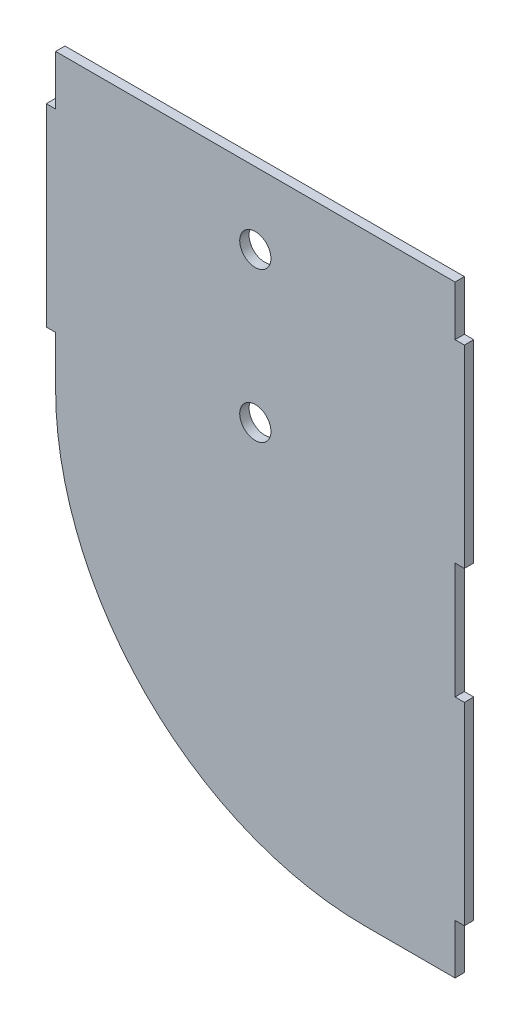
SolidWorks part; units mm, degrees
ref_plane "Front Plane" through (0, 0, 0) normal (0, 0, 1) x (1, 0, 0)
ref_plane "Top Plane" through (0, 0, 0) normal (0, 1, 0) x (1, 0, 0)
ref_plane "Right Plane" through (0, 0, 0) normal (1, 0, 0) x (0, 0, -1)
sketch "Sketch1" plane through (0, 0, 0) normal (0, 0, 1) x (1, 0, 0)
  line L0 (0, 74.6125) -> (-203.2, 74.6125)
  line L1 (0, 87.3125) -> (4.7625, 87.3125) construction
  line L2 (-203.2, 65.0875) -> (-203.2, -65.0875) construction
  line L4 (-203.2, 74.6125) -> (-203.2, 49.2125)
  line L5 (-203.2, 49.2125) -> (-207.9625, 49.2125)
  line L6 (-45.7679, -232.0446) -> (0, -232.0446)
  line L7 (0, -238.3946) -> (0, -206.6446) construction
  line L8 (0, -232.0446) -> (0, -206.6446)
  line L9 (-203.2, -74.6125) -> (-203.2, -49.2125)
  line L10 (-203.2, -49.2125) -> (-207.9625, -49.2125)
  line L11 (0, -206.6446) -> (4.7625, -206.6446) construction
  line L12 (-207.9625, -49.2125) -> (-207.9625, 49.2125)
  line L14 (0, -206.6446) -> (4.7625, -206.6446)
  line L15 (0, 65.0875) -> (0, 80.9625) construction
  line L16 (0, 74.6125) -> (0, 49.2125)
  line L17 (0, -65.0875) -> (0, 65.0875) construction
  line L18 (4.7625, -206.6446) -> (4.7625, -108.2196)
  line L20 (4.7625, -108.2196) -> (0, -108.2196)
  line L22 (0, -108.2196) -> (0, -49.2125) construction
  line L23 (0, -108.2196) -> (0, -49.2125)
  line L24 (0, -49.2125) -> (4.7625, -49.2125)
  line L25 (4.7625, -49.2125) -> (4.7625, 49.2125)
  line L26 (4.7625, 49.2125) -> (0, 49.2125)
  line L27 (4.7625, -244.7446) -> (0, -244.7446) construction
  arc A4 (-45.7679, -232.0446) -> (-203.2, -74.6125) centre (-45.7679, -74.6125) cw
  dimension "D1" = 12.7
  dimension "D2" = 12.7
extrude "Extrude1" add sketch "Sketch1" against normal blind 4.7625
sketch "Sketch2" plane through (0, 0, 0) normal (0, 0, 1) x (1, 0, 0)
  line L0 (-101.6, 38.1) -> (-101.6, -38.1) construction
  line L1 (0, 74.6125) -> (-203.2, 74.6125) construction
  line L3 (0, 0) -> (-101.6, 0) construction
  circle A0 centre (-101.6, 38.1) radius 7.9375
  circle A1 centre (-101.6, -38.1) radius 7.9375
  point P5 (-101.6, 74.6125)
  dimension "D2" = 76.2
  dimension "D1" = 15.875
extrude "Cut-Extrude1" cut sketch "Sketch2" against normal up to next
